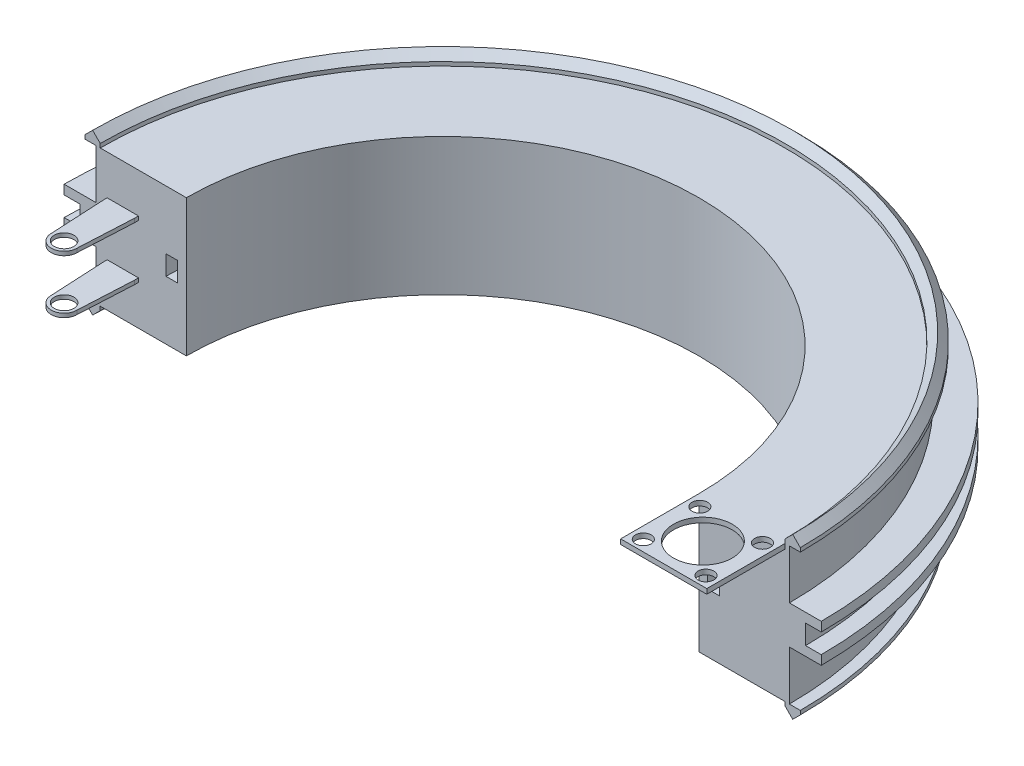
SolidWorks part; units mm, degrees
ref_plane "Front Plane" through (0, 0, 0) normal (0, 0, 1) x (1, 0, 0)
ref_plane "Top Plane" through (0, 0, 0) normal (0, 1, 0) x (1, 0, 0)
ref_plane "Right Plane" through (0, 0, 0) normal (1, 0, 0) x (0, 0, -1)
sketch "Sketch1" plane through (0, 0, 0) normal (0, 0, 1) x (1, 0, 0)
  line L0 (0, 22.1426) -> (0, -20.7935) construction
  line L1 (0, 22.1426) -> (0, -12.8574)
  line L2 (0, -12.8574) -> (-22, -12.8574)
  line L10 (-31.2312, -0.2335) -> (-31.2312, 2.1426)
  line L11 (-31.2312, 2.1426) -> (-27.2312, 2.1426)
  line L12 (-27.2312, 2.1426) -> (-27.2312, 7.1426)
  line L13 (-27.2312, 7.1426) -> (-31.2312, 7.1426)
  line L14 (-31.2312, 7.1426) -> (-31.2312, 9.5187)
  line L22 (-22, 22.1426) -> (0, 22.1426)
  line L24 (-22, 22.1426) -> (-22, 23.1426)
  line L25 (-5.2312, 7.1426) -> (-2.2312, 7.1426)
  line L26 (-5.2312, 7.1426) -> (-5.2312, 2.1426)
  line L27 (-5.2312, 2.1426) -> (-2.2312, 2.1426)
  line L28 (-2.2312, 7.1426) -> (-2.2312, 2.1426)
  line L29 (-22, 23.1426) -> (-23.9445, 25.0871)
  line L30 (-23.9445, 25.0871) -> (-25.8891, 23.1426)
  line L31 (-25.8891, 23.1426) -> (-25.8891, 22.1426)
  line L32 (-25.8891, 22.1426) -> (-23.0909, 22.1426)
  line L33 (-23.0909, 22.1426) -> (-23.0909, 9.5187)
  line L34 (-23.0909, 9.5187) -> (-31.2312, 9.5187)
  line L35 (-31.2312, -0.2335) -> (-23.0909, -0.2335)
  line L36 (-23.0909, -0.2335) -> (-23.0909, -12.8574)
  line L37 (-23.0909, -12.8574) -> (-25.8891, -12.8574)
  line L38 (-25.8891, -12.8574) -> (-25.8891, -13.8574)
  line L39 (-25.8891, -13.8574) -> (-23.9445, -15.802)
  line L40 (-23.9445, -15.802) -> (-22, -13.8574)
  line L41 (-22, -13.8574) -> (-22, -12.8574)
  dimension "D1" = 35
  dimension "D2" = 22
  dimension "D3" = 1
  dimension "D4" = 2.75
  dimension "D5" = 2.75
  dimension "D8" = 5
  dimension "D9" = 4
  dimension "D10" = 5
  dimension "D11" = 3
  dimension "D12" = 22
sketch "Sketch3" plane through (0, 0, 0) normal (0, 1, 0) x (1, 0, 0)
  arc A0 (0, 0) -> (130.92, 0) centre (65.46, 0) cw
sweep "Sweep3" add profiles "Sketch1" path "Sketch3"
sketch "Sketch13" plane through (0, 0, 0) normal (0, 0, 1) x (1, 0, 0)
  line L4 (-5.2312, 4.6426) -> (-5.2312, 18.9333) construction
  line L5 (-5.2312, 2.1426) -> (-5.2312, 7.1426) construction
  line L6 (-5.2312, 18.9333) -> (-5.2312, -5.0069) construction
  line L7 (-27.2312, 2.1426) -> (-5.2312, 2.1426) construction
  line L8 (-27.2312, 7.1426) -> (-5.2312, 7.1426) construction
  line L9 (-16.2312, 7.1426) -> (-16.2312, 2.1426) construction
  line L10 (-20.2312, 10.9926) -> (-12.2312, 10.9926)
  line L11 (-20.2312, 10.9926) -> (-16.2312, 10.9926)
  line L12 (-12.2312, 10.9926) -> (-12.2312, 11.9926)
  line L13 (-20.2312, 10.9926) -> (-20.2312, 11.9926)
  line L14 (-20.2312, 11.9926) -> (-12.2312, 11.9926)
  line L15 (-27.2312, 4.6426) -> (-5.2312, 4.6426) construction
  line L16 (-27.2312, 7.1426) -> (-27.2312, 2.1426) construction
  line L17 (-20.2312, -1.7074) -> (-20.2312, -2.7074)
  line L18 (-20.2312, -2.7074) -> (-12.2312, -2.7074)
  line L19 (-12.2312, -1.7074) -> (-12.2312, -2.7074)
  line L20 (-20.2312, -1.7074) -> (-12.2312, -1.7074)
  dimension "D1" = 8
  dimension "D2" = 4
  dimension "D3" = 1
  dimension "D4" = 6.35
extrude "Boss-Extrude1" add sketch "Sketch13" along normal blind 1 contours L14 L13 L10 L12 | L20 L17 L18 L19 region at (-16.2312, 11.4926, 0) region at (-16.2312, -2.2074, 0)
sketch "Sketch15" plane through (0, 11.9926, 0) normal (0, 1, 0) x (1, 0, 0)
  line L0 (-19.5054, -15) -> (-20.2312, -1)
  line L1 (-20.2312, 0) -> (-20.2312, -15) construction
  line L2 (-12.2312, 0) -> (-12.2312, -15) construction
  line L3 (-20.2312, -15) -> (-12.2312, -15) construction
  line L4 (-12.957, -15) -> (-12.2312, -1)
  circle A0 centre (-16.2312, -15) radius 2.5
  circle A1 centre (-16.2312, -15) radius 3.2742
  line M8 (-20.2312, -1) -> (-12.2312, -1)
extrude "Boss-Extrude4" add sketch "Sketch15" against normal blind 1 contours A1 A0 | A1 L4 L0 M8 region at (-16.2312, 11.9926, 6.6096) region at (-16.2312, 11.9926, 11.8184)
ref_plane "Plane3" through (0, 4.6426, 0) normal (0, 1, 0) x (1, 0, 0)
mirror "Mirror3" about plane through (0, 4.6426, 0) normal (0, 1, 0) of "Boss-Extrude4", "Boss-Extrude1"
sketch "Sketch17" plane through (0, 0, 0) normal (0, 0, 1) x (1, 0, 0)
  line L0 (130.92, 22.1426) -> (152.92, 22.1426)
  line L1 (152.92, 22.1426) -> (152.92, 20.8845)
  line L2 (152.92, 20.8845) -> (130.92, 20.8845)
  line L3 (130.92, -12.8574) -> (130.92, 22.1426) construction
  line L4 (130.92, 20.8845) -> (130.92, 22.1426)
extrude "Boss-Extrude5" add sketch "Sketch17" along normal blind 20
sketch "Sketch18" plane through (0, 20.8845, 0) normal (0, -1, 0) x (1, 0, 0)
  line L0 (141.92, 20) -> (141.92, 0) construction
  line L1 (130.92, 20) -> (152.92, 20) construction
  line L2 (130.92, 0) -> (152.92, 0) construction
  line L3 (130.92, 10) -> (152.92, 10) construction
  line L4 (130.92, 20) -> (130.92, 0) construction
  line L5 (152.92, 20) -> (152.92, 0) construction
  circle A0 centre (141.92, 10) radius 7.5
  circle A1 centre (133.923, 17.2171) radius 2
  circle A2 centre (149.9169, 17.2171) radius 2
  circle A3 centre (133.923, 2.7829) radius 2
  circle A4 centre (149.9169, 2.7829) radius 2
extrude "Cut-Extrude2" cut sketch "Sketch18" against normal blind 2 contours A0 | A1 | A2 | A3 | A4
